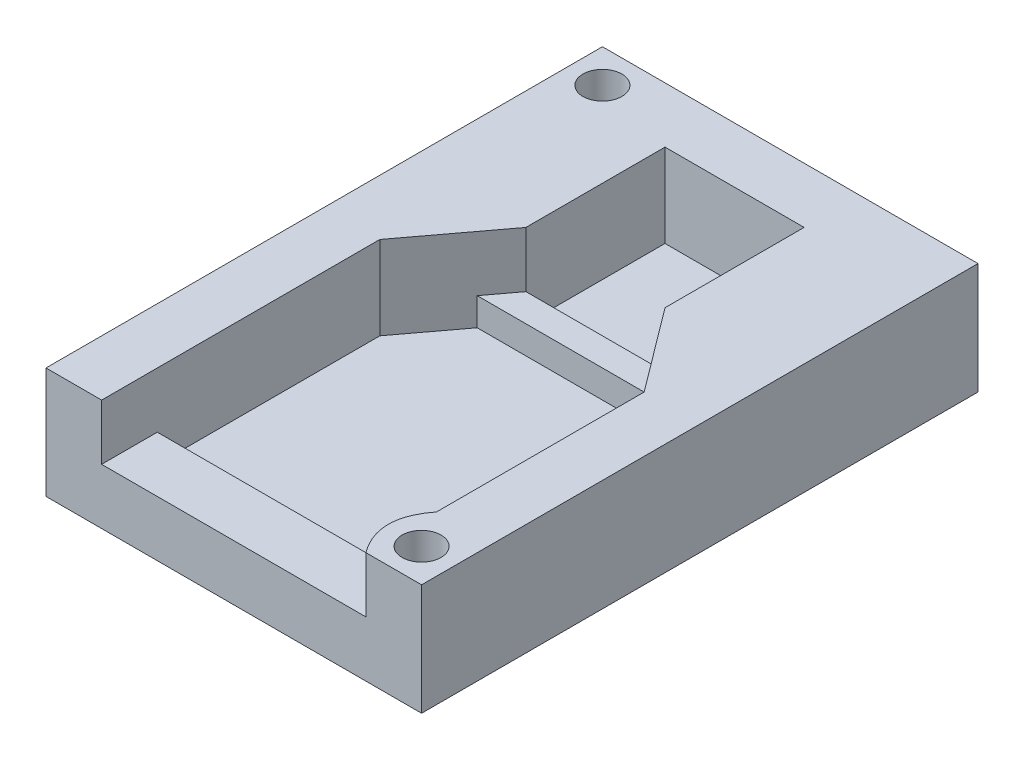
SolidWorks part; units mm, degrees
ref_plane "Front Plane" through (0, 0, 0) normal (0, 0, 1) x (1, 0, 0)
ref_plane "Top Plane" through (0, 0, 0) normal (0, 1, 0) x (1, 0, 0)
ref_plane "Right Plane" through (0, 0, 0) normal (1, 0, 0) x (0, 0, -1)
sketch "Sketch1" plane through (0, 0, 0) normal (0, 1, 0) x (1, 0, 0)
  line L1 (0, 0) -> (13.5, 0)
  line L2 (0, 0) -> (0, 20)
  line L3 (0, 20) -> (13.5, 20)
  line L4 (13.5, 0) -> (13.5, 20)
  dimension "D1" = 20
  dimension "D2" = 13.5
extrude "Boss-Extrude1" add sketch "Sketch1" along normal blind 1
sketch "Sketch2" plane through (0, 1, 0) normal (0, 1, 0) x (1, 0, 0)
  line L0 (2, 10) -> (2, 2)
  line L1 (0, 20) -> (13.5, 20)
  line L2 (0, 20) -> (0, 0)
  line L3 (0, 0) -> (2, 0)
  line L4 (13.5, 20) -> (13.5, 0)
  line L5 (4.25, 13) -> (2, 10)
  line L6 (4.25, 18) -> (4.25, 13)
  line L7 (2, 2) -> (2, 0)
  line L8 (9.25, 18) -> (9.25, 13)
  line L10 (11.5, 10) -> (11.5, 2.5356)
  line L11 (4.25, 18) -> (9.25, 18)
  line L12 (2, 18) -> (11.5, 18) construction
  line L13 (9.25, 13) -> (11.5, 10)
  line L14 (2, 18) -> (2, 2) construction
  line L15 (2, 2) -> (11.5, 2) construction
  line L16 (11.5, 18) -> (11.5, 2) construction
  line L17 (11.5, 0) -> (13.5, 0)
  line L19 (0, 0) -> (13.5, 0) construction
  spline S0 degree 2 poles (11.5, 2.5356) (10.5366, 1.3002) (11.5, 0) knots 0 0 0 1 1 1
  dimension "D1" = 5
  dimension "D2" = 5
  dimension "D4" = 4.25
  dimension "D5" = 4.25
  dimension "D6" = 2
extrude "Boss-Extrude2" add sketch "Sketch2" along normal blind 3
sketch "Sketch3" plane through (0, 1, 0) normal (0, 1, 0) x (1, 0, 0)
  line L0 (4.25, 13) -> (9.25, 13)
  line L1 (9.25, 13) -> (10, 12)
  line L2 (9.25, 13) -> (11.5, 10) construction
  line L3 (10, 12) -> (3.5, 12)
  line L4 (2, 10) -> (4.25, 13) construction
  line L5 (3.5, 12) -> (4.25, 13)
  line L6 (13.5, 20) -> (0, 20) construction
  line L7 (13.5, 0) -> (13.5, 20) construction
  line L8 (0, 20) -> (0, 0) construction
  dimension "D1" = 1
  dimension "D2" = 7
  dimension "D3" = 4.25
  dimension "D4" = 3.5
extrude "Boss-Extrude3" add sketch "Sketch3" along normal blind 1
sketch "Sketch4" plane through (0, 0, 0) normal (0, -1, 0) x (1, 0, 0)
  line L0 (0, -20) -> (0, 0) construction
  line L1 (13.5, -20) -> (0, -20) construction
  line L2 (0, 0) -> (13.5, 0) construction
  line L3 (13.5, 0) -> (13.5, -20) construction
  circle A0 centre (1.2, -18.8) radius 0.7
  circle A1 centre (12.3, -1.2) radius 0.7
  dimension "D1" = 1.2
  dimension "D2" = 1.2
  dimension "D3" = 1.2
  dimension "D4" = 1.2
extrude "Cut-Extrude1" cut sketch "Sketch4" against normal blind 11.5 from offset 1 offset against normal yes
sketch "Sketch5" plane through (0, 1, 0) normal (0, 1, 0) x (1, 0, 0)
  line L0 (11.5, 10) -> (11.5, 2.5356) construction
  line L1 (2, 0) -> (11.5, 0)
  line L2 (2, 0) -> (2, 2)
  line L3 (2, 2) -> (11.5, 2)
  line L4 (11.5, 0) -> (11.5, 2)
  dimension "D1" = 2
extrude "Boss-Extrude4" add sketch "Sketch5" along normal blind 1
